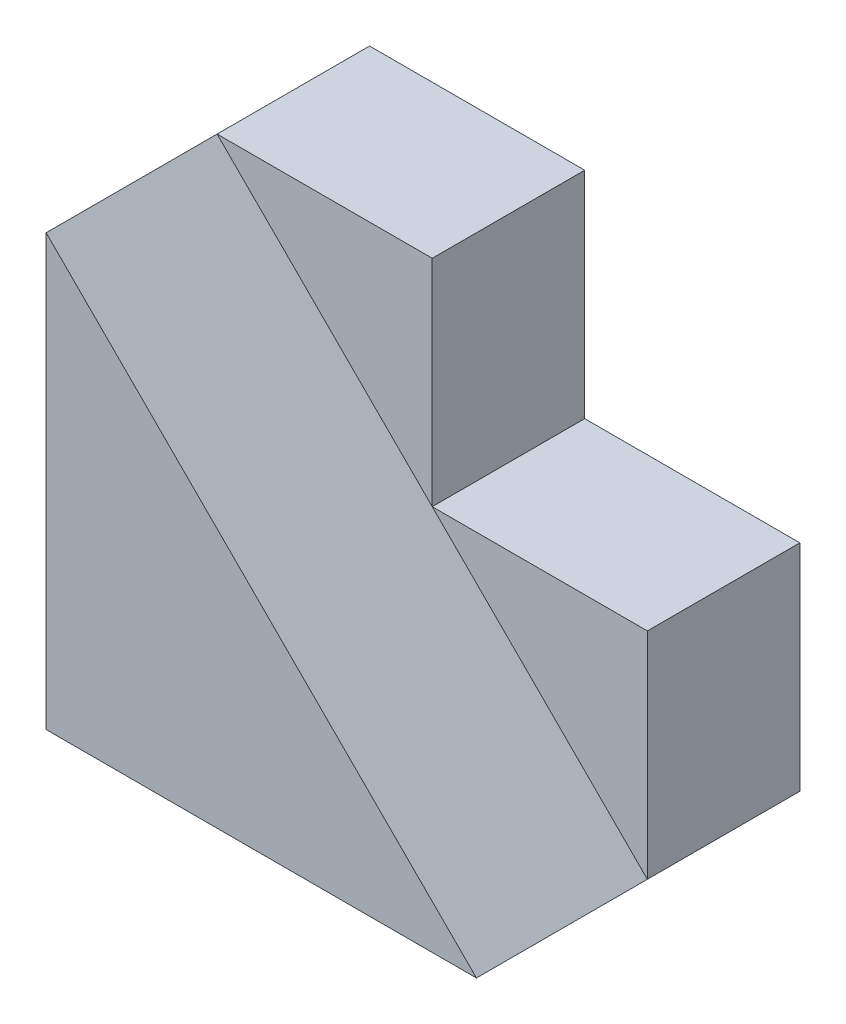
SolidWorks part; units mm, degrees
ref_plane "Front Plane" through (0, 0, 0) normal (0, 0, 1) x (1, 0, 0)
ref_plane "Top Plane" through (0, 0, 0) normal (0, 1, 0) x (1, 0, 0)
ref_plane "Right Plane" through (0, 0, 0) normal (1, 0, 0) x (0, 0, -1)
sketch "Sketch1" plane through (0, 0, 0) normal (0, 0, 1) x (1, 0, 0)
  line L0 (-21.2451, 35.5731) -> (-21.2451, -14.4269)
  line L1 (-21.2451, -14.4269) -> (28.7549, -14.4269)
  line L2 (28.7549, -14.4269) -> (-21.2451, 35.5731)
  line L3 (-21.2451, 35.5731) -> (3.7549, 35.5731)
  line L4 (3.7549, 35.5731) -> (3.7549, 10.5731)
  line L5 (3.7549, 10.5731) -> (28.7549, 10.5731)
  line L6 (28.7549, 10.5731) -> (28.7549, -14.4269)
  dimension "D1" = 50
  dimension "D2" = 50
  dimension "D3" = 25
  dimension "D4" = 25
  dimension "D5" = 25
  dimension "D6" = 25
extrude "Boss-Extrude3" add sketch "Sketch1" along normal blind 37.5812 contours L0 L1 L2
extrude "Boss-Extrude4" add sketch "Sketch1<9>" along normal blind 17.7187 contours L4 L3 L2 | L6 L5 L2 region at (-4.5784, 27.2398, 0) region at (20.4216, 2.2398, 0)
sketch "Sketch1<9>" plane through (0, 0, 0) normal (0, 0, 1) x (1, 0, 0) same geometry as "Sketch1"
